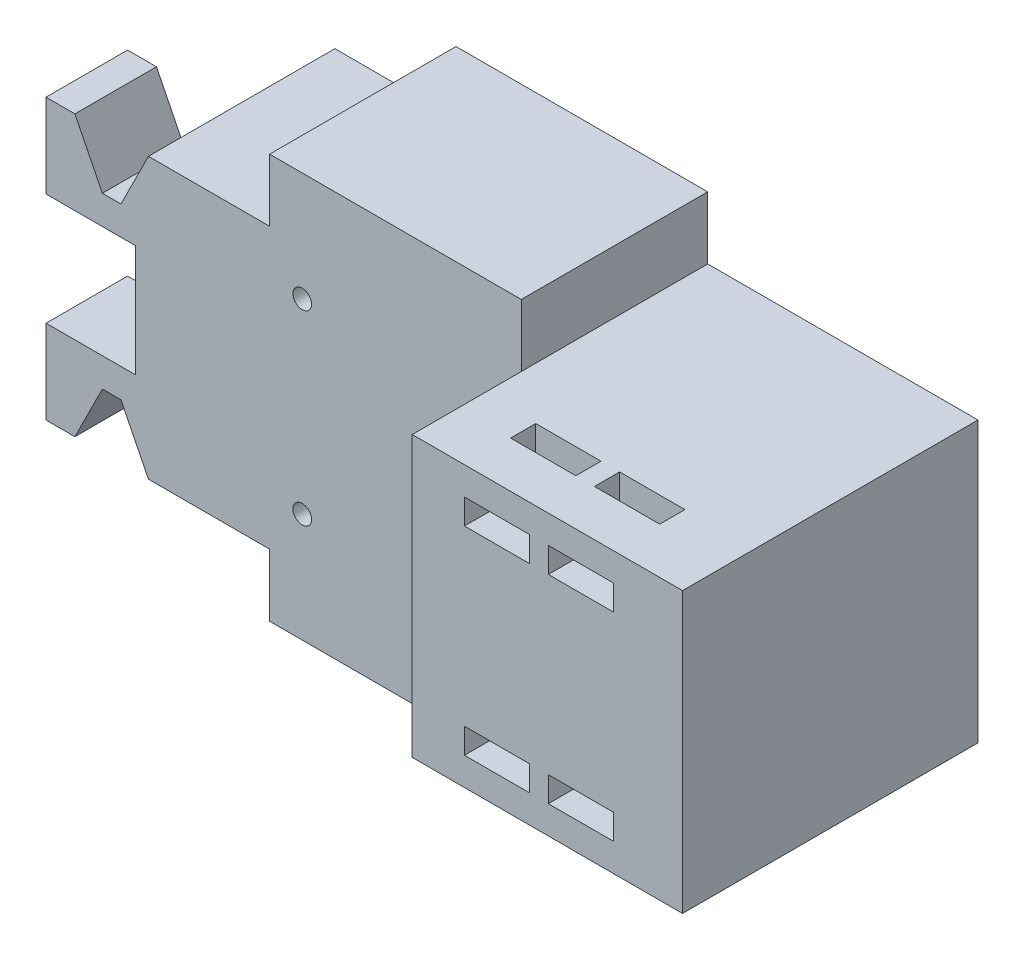
SolidWorks part; units mm, degrees
ref_plane "Front Plane" through (0, 0, 0) normal (0, 0, 1) x (1, 0, 0)
ref_plane "Top Plane" through (0, 0, 0) normal (0, 1, 0) x (1, 0, 0)
ref_plane "Right Plane" through (0, 0, 0) normal (1, 0, 0) x (0, 0, -1)
sketch "BackFace-Sketch1" plane through (0, 0, 0) normal (0, 0, 1) x (1, 0, 0)
  line L0 (0, 0) -> (0, 9)
  line L1 (0, 9) -> (9.6, 9)
  line L2 (9.6, 9) -> (9.6, 21)
  line L3 (9.6, 21) -> (0, 21)
  line L4 (0, 21) -> (0, 30)
  line L5 (0, 30) -> (3.1, 30)
  line L6 (3.1, 30) -> (6.05, 24.096)
  line L7 (6.05, 24.096) -> (8.04, 24.096)
  line L8 (8.04, 24.096) -> (10.99, 30)
  line L9 (10.99, 30) -> (23.99, 30)
  line L10 (79.99, 30) -> (79.99, 0)
  line L11 (79.99, 0) -> (50.99, 0)
  line L12 (10.99, 0) -> (8.04, 5.904)
  line L13 (8.04, 5.904) -> (6.05, 5.904)
  line L14 (6.05, 5.904) -> (3.1, 0)
  line L15 (3.1, 0) -> (0, 0)
  line L16 (23.99, 0) -> (23.99, -6.7)
  line L17 (23.99, -6.7) -> (50.99, -6.7)
  line L18 (50.99, -6.7) -> (50.99, 0)
  line L19 (23.99, 30) -> (23.99, 36.7)
  line L20 (23.99, 36.7) -> (50.99, 36.7)
  line L21 (50.99, 36.7) -> (50.99, 30)
  line L22 (50.99, 30) -> (79.99, 30)
  line L23 (23.99, 0) -> (10.99, 0)
  point P13 (4.8, 9)
  point P17 (4.575, 2.952)
  point P18 (7.045, 24.096)
  point P19 (7.045, 5.904)
  dimension "D1" = 3.1
  dimension "D2" = 9
  dimension "D4" = 6.6
  dimension "D5" = 1.99
  dimension "D7" = 30
  dimension "D8" = 9.6
  dimension "D6" = 2.95
  dimension "D9" = 27
  dimension "D10" = 43.4
  dimension "D11" = 13
  dimension "D3" = 29
extrude "Boss-Extrude1" add sketch "BackFace-Sketch1" along normal blind 20
sketch "EarKnotch-Sketch2" plane through (0, 0, 0) normal (0, 0, -1) x (-1, 0, 0)
  line L0 (-23.99, 30) -> (-10.99, 30) construction
  line L1 (0, 30) -> (-7.1, 30)
  line L2 (0, 30) -> (0, 0)
  line L3 (0, 0) -> (-7.1, 0)
  line L4 (-7.1, 30) -> (-7.1, 0)
  line L5 (-50.99, 0) -> (-79.99, 0) construction
  line L8 (0, 30) -> (0, 21) construction
  dimension "D1" = 7.1
extrude "EarKnotch-Cut-Extrude1" cut sketch "EarKnotch-Sketch2" against normal blind 11.25
sketch "TopHoles-Sketch3" plane through (0, 0, 0) normal (-1, 0, 0) x (0, 0, 1)
  line L0 (20, 30) -> (20, 21) construction
  line L1 (20, 30) -> (11.25, 30) construction
  line L2 (20, 0) -> (11.25, 0) construction
  circle A0 centre (15.5, 25.5) radius 2.3
  circle A1 centre (15.5, 4.5) radius 2.3
  dimension "D4" = 4.6
  dimension "D1" = 4.5
  dimension "D2" = 4.5
  dimension "D3" = 4.5
extrude "TopHoles-Cut-Extrude2" cut sketch "TopHoles-Sketch3" against normal blind 4
sketch "FrontHoles-Sketch1" plane through (0, 0, 0) normal (0, 0, -1) x (-1, 0, 0)
  line L0 (-79.99, 0) -> (-79.99, 30) construction
  line L1 (-23.99, 30) -> (-10.99, 30) construction
  line L2 (-50.99, 0) -> (-79.99, 0) construction
  circle A0 centre (-55.49, 25) radius 2.25
  circle A1 centre (-55.49, 5) radius 2.25
  circle A2 centre (-43.49, 25) radius 2.25
  circle A3 centre (-43.49, 5) radius 2.25
  dimension "D2" = 4.5
  dimension "D1" = 24.5
  dimension "D3" = 12
  dimension "D4" = 5
  dimension "D5" = 5
extrude "FrontHoles-Cut-Extrude1" cut sketch "FrontHoles-Sketch1" against normal blind 7
sketch "RearMountingHoles-Sketch2" plane through (0, 0, 20) normal (0, 0, 1) x (1, 0, 0)
  line L0 (50.99, 0) -> (79.99, 0) construction
  line L1 (23.99, 30) -> (10.99, 30) construction
  line L2 (23.99, 36.7) -> (23.99, 30) construction
  circle A0 centre (27.49, 25) radius 1
  circle A1 centre (27.49, 5) radius 1
  circle A2 centre (47.49, 25) radius 1
  circle A3 centre (47.49, 5) radius 1
  dimension "D6" = 2
  dimension "D2" = 20
  dimension "D3" = 5
  dimension "D1" = 20
  dimension "D4" = 5
  dimension "D5" = 3.5
extrude "RearMountingHoles-Cut-Extrude2" cut sketch "RearMountingHoles-Sketch2" against normal through all
sketch "BlockUnderRail-Sketch1" plane through (0, 0, 20) normal (0, 0, 1) x (1, 0, 0)
  line L0 (79.99, 0) -> (79.99, 30) construction
  line L1 (50.99, 30) -> (79.99, 30)
  line L2 (50.99, 30) -> (50.99, 0)
  line L3 (50.99, 0) -> (79.99, 0)
  line L4 (79.99, 30) -> (79.99, 0)
  line L5 (79.99, 30) -> (50.99, 30) construction
  line L6 (50.99, 30) -> (50.99, 36.7) construction
extrude "BlockUnderRail-Boss-Extrude2" add sketch "BlockUnderRail-Sketch1" along normal blind 11.7
sketch "RearRibbonHoles-Sketch2" plane through (0, 0, 31.7) normal (0, 0, 1) x (1, 0, 0)
  line L1 (56.59, 27) -> (63.59, 27)
  line L2 (56.59, 27) -> (56.59, 24.3)
  line L3 (56.59, 24.3) -> (63.59, 24.3)
  line L4 (63.59, 27) -> (63.59, 24.3)
  line L5 (65.59, 27) -> (72.59, 27)
  line L6 (65.59, 27) -> (65.59, 24.3)
  line L7 (65.59, 24.3) -> (72.59, 24.3)
  line L8 (72.59, 27) -> (72.59, 24.3)
  line L9 (56.59, 5.7) -> (63.59, 5.7)
  line L10 (56.59, 5.7) -> (56.59, 3)
  line L11 (56.59, 3) -> (63.59, 3)
  line L12 (63.59, 5.7) -> (63.59, 3)
  line L13 (65.59, 5.7) -> (72.59, 5.7)
  line L14 (65.59, 5.7) -> (65.59, 3)
  line L15 (65.59, 3) -> (72.59, 3)
  line L16 (72.59, 5.7) -> (72.59, 3)
  line L17 (79.99, 0) -> (79.99, 30) construction
  line L20 (50.99, 0) -> (79.99, 0) construction
  line L21 (79.99, 30) -> (50.99, 30) construction
  dimension "D3" = 2.7
  dimension "D4" = 7
  dimension "D5" = 2
  dimension "D2" = 3
  dimension "D1" = 3
  dimension "D6" = 7.4
extrude "RearRibbonHoles-Cut-Extrude1" cut sketch "RearRibbonHoles-Sketch2" against normal blind 7.65
sketch "LeftRibbonHoles-Sketch3" plane through (0, 0, 0) normal (0, -1, 0) x (1, 0, 0)
  line L0 (56.59, 24.05) -> (63.59, 24.05) construction
  line L1 (56.59, 26.75) -> (63.59, 26.75)
  line L2 (56.59, 26.75) -> (56.59, 24.05)
  line L3 (56.59, 24.05) -> (63.59, 24.05)
  line L4 (63.59, 26.75) -> (63.59, 24.05)
  line L5 (65.59, 26.75) -> (72.59, 26.75)
  line L6 (65.59, 26.75) -> (65.59, 24.05)
  line L7 (65.59, 24.05) -> (72.59, 24.05)
  line L8 (72.59, 26.75) -> (72.59, 24.05)
  line L9 (56.59, 24.05) -> (56.59, 31.7) construction
  line L10 (63.59, 24.05) -> (63.59, 31.7) construction
  line L11 (65.59, 24.05) -> (65.59, 31.7) construction
  line L12 (72.59, 24.05) -> (72.59, 31.7) construction
  dimension "D1" = 2.7
sketch "RightRibbonHoles-Sketch4" plane through (0, 30, 0) normal (0, 1, 0) x (1, 0, 0)
  line L0 (72.59, -24.05) -> (65.59, -24.05) construction
  line L9 (63.59, -24.05) -> (56.59, -24.05) construction
  line L10 (56.59, -24.05) -> (56.59, -31.7) construction
  line L11 (65.59, -24.05) -> (65.59, -31.7) construction
  line L13 (72.59, -24.05) -> (72.59, -31.7) construction
  line L14 (56.59, -24.05) -> (63.59, -24.05)
  line L15 (56.59, -24.05) -> (56.59, -26.75)
  line L16 (56.59, -26.75) -> (63.59, -26.75)
  line L17 (63.59, -24.05) -> (63.59, -26.75)
  line L18 (65.59, -24.05) -> (72.59, -24.05)
  line L19 (65.59, -24.05) -> (65.59, -26.75)
  line L20 (65.59, -26.75) -> (72.59, -26.75)
  line L21 (72.59, -24.05) -> (72.59, -26.75)
  line L22 (63.59, -24.05) -> (63.59, -31.7) construction
  line L23 (63.59, -24.05) -> (56.59, -24.05) construction
  line L26 (55.51, -26.7) -> (33.1572, -26.7) construction
  line L27 (50.99, -28.35) -> (33.1572, -28.35) construction
  line L28 (50.99, -20) -> (23.99, -20) construction
  dimension "D1" = 2.7
  dimension "D2" = 8.35
extrude "RightRibbonHoles-Cut-Extrude2" cut sketch "RightRibbonHoles-Sketch4" against normal blind 5.7
extrude "LeftRibbonHoles-Cut-Extrude2" cut sketch "LeftRibbonHoles-Sketch3" against normal blind 5.7
equation "\"CarrierWidth\"= \"LinearGBWidthWithBumpers\" - 2mm"
equation "\"LinearGBWidth\"= 27mm'Spec"
equation "\"D10@BackFace-Sketch1\"=\"CarrierWidth\""
equation "\"LinearGBWidthWithBumpers\"= 45.4mm"
equation "\"LinearGBMountHolesXDistance\"= 20mm'Spec"
equation "\"LinearGBMountHolesYDistance\"= 20mm'Spec"
equation "\"D1@RearMountingHoles-Sketch2\"=\"LinearGBMountHolesXDistance\""
equation "\"D2@RearMountingHoles-Sketch2\"=\"LinearGBMountHolesYDistance\""
equation "\"D5@RearMountingHoles-Sketch2\"= ( \"LinearGBWidth\" - \"LinearGBMountHolesYDistance\" ) / 2"
equation "\"CarrierRibbonHoleWidth\"= 7mm"
equation "\"CarrierRibbonHoleHeight\"= 2.7mm"
equation "\"CarrierRibbonHoleDistance\"= 2mm"
equation "\"CarrierRibbonHoleOffsetFromSide\"= 3.0mm"
equation "\"CarrierDepth\"= 20mm"
equation "\"D1@Boss-Extrude1\"=\"CarrierDepth\""
equation "\"D3@RearRibbonHoles-Sketch2\" = \"CarrierRibbonHoleHeight\""
equation "\"D4@RearRibbonHoles-Sketch2\" = \"CarrierRibbonHoleWidth\""
equation "\"D5@RearRibbonHoles-Sketch2\" = \"CarrierRibbonHoleDistance\""
equation "\"D9@BackFace-Sketch1\"=\"LinearGBWidth\""
equation "\"D2@RearRibbonHoles-Sketch2\"=\"CarrierRibbonHoleOffsetFromSide\""
equation "\"D1@RearRibbonHoles-Sketch2\"=\"CarrierRibbonHoleOffsetFromSide\""
equation "\"D1@RightRibbonHoles-Cut-Extrude2\" = \"CarrierRibbonHoleOffsetFromSide\" + \"CarrierRibbonHoleHeight\""
equation "\"LinearRailHeight\"= 8mm'Spec"
equation "\"LinearGBDepth\"= 10mm'Spec"
equation "\"D1@BlockUnderRail-Boss-Extrude2\"=\"MiddleOfGBAndLinearRail\" +  \"CarrierRibbonHoleHeight\""
equation "\"D1@LeftRibbonHoles-Cut-Extrude2\" = \"CarrierRibbonHoleOffsetFromSide\" + \"CarrierRibbonHoleHeight\""
equation "\"D1@RightRibbonHoles-Sketch4\"=\"CarrierRibbonHoleHeight\""
equation "\"D1@RearRibbonHoles-Cut-Extrude1\"=\"MiddleOfGBAndLinearRail\" - \"CarrierRibbonHoleHeight\"/2mm"
equation "\"D1@LeftRibbonHoles-Sketch3\"=\"CarrierRibbonHoleHeight\""
equation "\"MiddleOfGBAndLinearRail\"= \"LinearGBDepth\" / 2 + \"LinearRailHeight\" / 2"
equation "\"CarrierUpperBodyLength\"= 13mm"
equation "\"CarrierLowerBodyLength\"= 29mm"
equation "\"D3@BackFace-Sketch1\"=\"CarrierLowerBodyLength\""
equation "\"D11@BackFace-Sketch1\"=\"CarrierUpperBodyLength\""
equation "\"CarrierRibbonHoleOffsetFromBottom\"= 7.4mm"
equation "\"D6@RearRibbonHoles-Sketch2\"=\"CarrierRibbonHoleOffsetFromBottom\""
